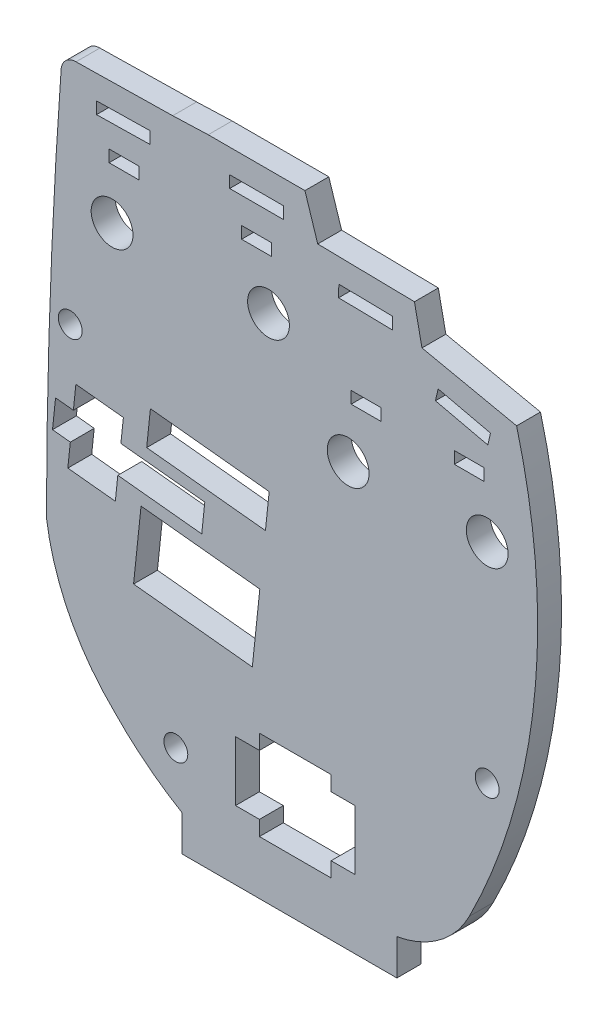
SolidWorks part; units mm, degrees
ref_plane "Front Plane" through (0, 0, 0) normal (0, 0, 1) x (1, 0, 0)
ref_plane "Top Plane" through (0, 0, 0) normal (0, 1, 0) x (1, 0, 0)
ref_plane "Right Plane" through (0, 0, 0) normal (1, 0, 0) x (0, 0, -1)
sketch "Sketch1" plane through (0, 0, 0) normal (0, 0, 1) x (1, 0, 0)
  line L0 (7.2814, 78.51) -> (7.2814, 76.51)
  line L1 (16.2814, 78.51) -> (7.2814, 78.51)
  line L2 (7.2814, 76.51) -> (16.2814, 76.51)
  line L3 (16.2814, 76.51) -> (16.2814, 78.51)
  line L4 (8.26, -2.5) -> (12.26, -2.5)
  line L5 (-18.4588, 82.0157) -> (-2.2613, 82.2984)
  line L6 (19.8814, 82.51) -> (3.6814, 82.51)
  line L7 (24.26, 0) -> (12.26, 0)
  line L8 (22.0243, 75.841) -> (38.2219, 75.5583)
  line L9 (44.9074, 57.3216) -> (49.9074, 57.3216)
  line L10 (-0.7186, -18) -> (-0.7186, -24)
  line L11 (44.9074, 55.3216) -> (49.9074, 55.3216)
  line L12 (49.9074, 55.3216) -> (49.9074, 57.3216)
  line L13 (44.9074, 57.3216) -> (44.9074, 55.3216)
  line L14 (-15.0579, 78.0715) -> (-6.0592, 78.2285)
  line L15 (-15.0579, 78.0715) -> (-15.023, 76.0718)
  line L16 (-15.023, 76.0718) -> (-6.0243, 76.2288)
  line L17 (-6.0243, 76.2288) -> (-6.0592, 78.2285)
  line L18 (27.6231, 57.3998) -> (32.6231, 57.3998)
  line L19 (27.6231, 55.3998) -> (32.6231, 55.3998)
  line L20 (32.6231, 55.3998) -> (32.6231, 57.3998)
  line L21 (27.6231, 57.3998) -> (27.6231, 55.3998)
  line L22 (9.2814, 72.1512) -> (14.2814, 72.1512)
  line L23 (25.554, 71.7788) -> (25.5191, 69.7791)
  line L24 (25.5191, 69.7791) -> (34.5177, 69.622)
  line L25 (9.2814, 70.1512) -> (14.2814, 70.1512)
  line L26 (34.5526, 71.6217) -> (25.554, 71.7788)
  line L27 (34.5177, 69.622) -> (34.5526, 71.6217)
  line L28 (19.8814, 82.51) -> (22.0243, 75.841)
  line L29 (14.2814, 70.1512) -> (14.2814, 72.1512)
  line L30 (39.4844, 69.484) -> (55.3304, 66.1158)
  line L31 (9.2814, 72.1512) -> (9.2814, 70.1512)
  line L32 (50.9604, 62.875) -> (42.1911, 64.8996)
  line L33 (13.8929, 35.8521) -> (13.2658, 29.885)
  line L34 (42.1911, 64.8996) -> (41.7412, 62.9508)
  line L35 (-12.9189, 72.1512) -> (-7.9189, 72.1512)
  line L36 (-2.2613, 82.2984) -> (3.6814, 82.51)
  line L37 (38.2219, 75.5583) -> (39.4844, 69.484)
  line L38 (-12.9189, 70.1512) -> (-7.9189, 70.1512)
  line L39 (41.7412, 62.9508) -> (50.5105, 60.9263)
  line L40 (-7.9189, 70.1512) -> (-7.9189, 72.1512)
  line L41 (-12.9189, 72.1512) -> (-12.9189, 70.1512)
  line L42 (50.5105, 60.9263) -> (50.9604, 62.875)
  line L43 (13.8929, 35.8521) -> (-5.9975, 37.9427)
  line L44 (12.325, 20.9343) -> (11.0707, 9)
  line L45 (24.26, 0) -> (24.26, -2.5)
  line L46 (-6.6247, 31.9755) -> (13.2658, 29.885)
  line L47 (24.26, -15) -> (12.26, -15)
  line L48 (2.5978, 24.0682) -> (3.11, 28.9414)
  line L49 (-22.396, 26.6952) -> (-21.8838, 31.5683)
  line L50 (3.11, 28.9414) -> (-10.9441, 30.4185)
  line L51 (-19.8305, 22.4035) -> (-19.4124, 26.3816)
  line L52 (-22.396, 26.6952) -> (-19.4124, 26.3816)
  line L53 (-11.4563, 25.5453) -> (2.5978, 24.0682)
  line L54 (-10.9441, 30.4185) -> (-10.526, 34.3966)
  line L55 (-11.8744, 21.5673) -> (-19.8305, 22.4035)
  line L56 (-6.6247, 31.9755) -> (-5.9975, 37.9427)
  line L57 (-18.4821, 35.2328) -> (-18.9002, 31.2547)
  line L58 (-10.526, 34.3966) -> (-18.4821, 35.2328)
  line L59 (-18.9002, 31.2547) -> (-21.8838, 31.5683)
  line L60 (-11.8744, 21.5673) -> (-11.4563, 25.5453)
  line L61 (-7.5654, 23.0248) -> (12.325, 20.9343)
  line L62 (-8.8198, 11.0906) -> (11.0707, 9)
  line L63 (12.26, -15) -> (12.26, -12.5)
  line L64 (8.26, -12.5) -> (8.26, -2.5)
  line L65 (-7.5654, 23.0248) -> (-8.8198, 11.0906)
  line L66 (-0.7186, -24) -> (35.2814, -24)
  line L67 (8.26, -12.5) -> (12.26, -12.5)
  line L68 (12.26, -2.5) -> (12.26, 0)
  line L69 (28.26, -12.5) -> (24.26, -12.5)
  line L70 (28.26, -12.5) -> (28.26, -2.5)
  line L71 (28.26, -2.5) -> (24.26, -2.5)
  line L72 (24.26, -12.5) -> (24.26, -15)
  line L73 (35.2814, -24) -> (35.2814, -18)
  arc A0 (-18.4588, 82.0157) -> (-20.9588, 79.5157) centre (-18.4588, 79.5157) ccw
  circle A1 centre (50.4074, 11.8216) radius 2
  arc A2 (-23.4103, 13.4121) -> (-20.9588, 79.5157) centre (915.2869, 11.697) cw
  circle A3 centre (-12.4189, 61.6512) radius 3.5
  circle A4 centre (13.7814, 61.6512) radius 3.5
  circle A5 centre (27.1231, 46.8216) radius 3.5
  circle A6 centre (50.4074, 46.8216) radius 3.5
  arc A7 (55.3304, 66.1158) -> (47.4074, -9) centre (-47.2858, 38.9637) cw
  circle A8 centre (-19.4215, 43.4564) radius 2
  circle A9 centre (-1.74, -9.1244) radius 2
  arc A10 (-23.4103, 13.4121) -> (-12.0645, -9) centre (14.8005, 18.678) ccw
  arc A11 (-12.0645, -9) -> (-0.7186, -18) centre (26.2565, 27.6579) ccw
  arc A12 (47.4074, -9) -> (35.2814, -18) centre (32.34, -1.3681) cw
  dimension "D6" = 4
  dimension "D15" = 8
  dimension "D16" = 19.2942
  dimension "D21" = 35
  dimension "D22" = 7
  dimension "D23" = 7
  dimension "D24" = 7
  dimension "D27" = 7
  dimension "D28" = 12
  dimension "D29" = 4
  dimension "D30" = 6
  dimension "D39" = 4
  dimension "D40" = 8
  dimension "D41" = 20
  dimension "D42" = 12
  dimension "D43" = 4
  dimension "D44" = 1.0143
  dimension "D47" = 14.1315
  dimension "D48" = 10
  dimension "D7" = 2.5
  dimension "D53" = 4
  dimension "D8" = 16.2
  dimension "D9" = 16.2
  dimension "D10" = 16.1975
  dimension "D11" = 16.2
  dimension "D12" = 5.9465
  dimension "D13" = 7.0048
  dimension "D14" = 6.2041
  dimension "D17" = 5
  dimension "D18" = 2
  dimension "D19" = 9
  dimension "D20" = 1.9997
  dimension "D25" = 9
  dimension "D26" = 2
  dimension "D31" = 5
  dimension "D32" = 2
  dimension "D33" = 9
  dimension "D34" = 1.9997
  dimension "D35" = 5
  dimension "D36" = 2
  dimension "D37" = 2
  dimension "D38" = 5
  dimension "D45" = 2
  dimension "D46" = 9
  dimension "D49" = 20
  dimension "D50" = 36
  dimension "D51" = 20
  dimension "D52" = 6
  dimension "D54" = 25.1315
  dimension "D55" = 4
  dimension "D56" = 11.0214
extrude "Boss-Extrude1" add sketch "Sketch1" along normal blind 4
